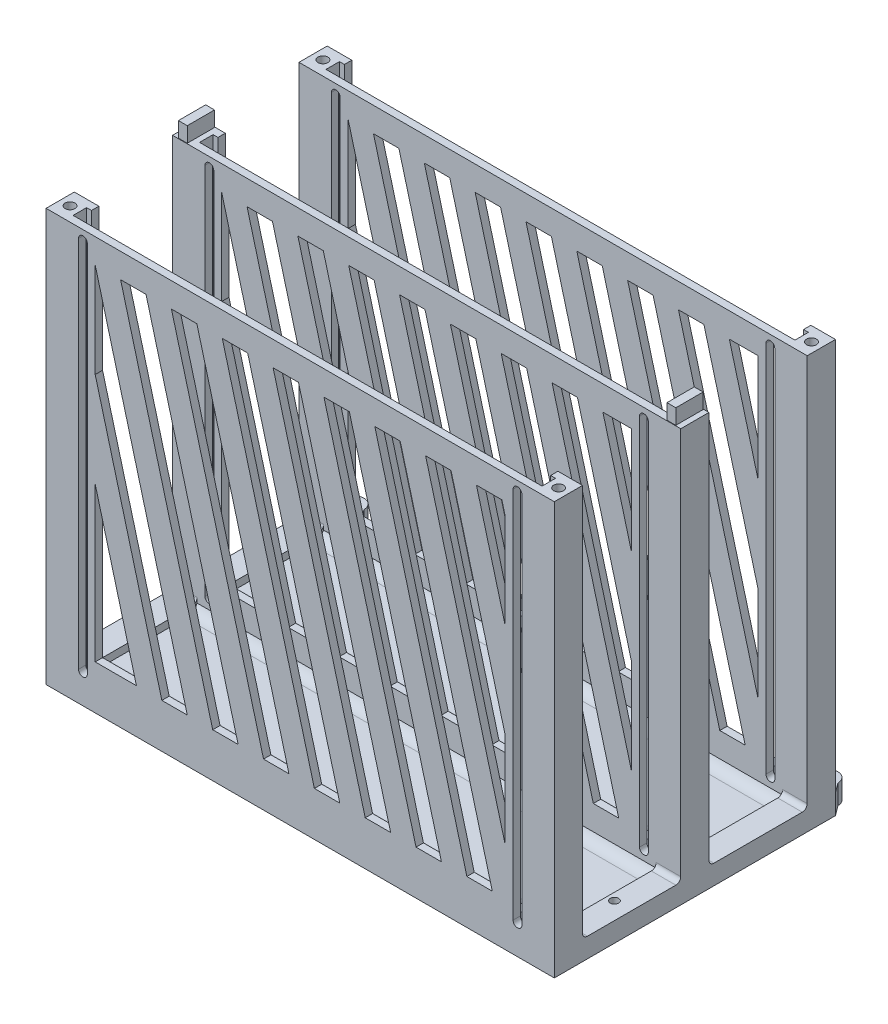
SolidWorks part; units mm, degrees
ref_plane "Front Plane" through (0, 0, 0) normal (0, 0, 1) x (1, 0, 0)
ref_plane "Top Plane" through (0, 0, 0) normal (0, 1, 0) x (1, 0, 0)
ref_plane "Right Plane" through (0, 0, 0) normal (1, 0, 0) x (0, 0, -1)
sketch "Sketch1" plane through (0, 0, 0) normal (0, 1, 0) x (1, 0, 0)
  line L0 (-95.5, 0) -> (95.5, 0) construction
  line L5 (-95.5, 2.75) -> (-93.5, 2.75)
  line L6 (-95.5, -2.75) -> (-95.5, 2.75)
  line L7 (-93.5, 2.75) -> (-93.5, 5.75)
  line L8 (-93.5, 5.75) -> (-103.5, 5.75)
  line L9 (-103.5, 5.75) -> (-103.5, -5.75)
  line L10 (-103.5, -5.75) -> (-93.5, -5.75)
  line L11 (-93.5, -5.75) -> (-93.5, -2.75)
  line L12 (-93.5, -2.75) -> (-95.5, -2.75)
  line L13 (-93.5, -2.75) -> (-93.5, -36.1204) construction
  line L14 (0, -55) -> (0, 55) construction
  line L15 (93.5, -5.75) -> (93.5, -2.75)
  line L16 (103.5, -5.75) -> (93.5, -5.75)
  line L17 (103.5, 5.75) -> (103.5, -5.75)
  line L18 (93.5, 5.75) -> (103.5, 5.75)
  line L19 (93.5, 2.75) -> (93.5, 5.75)
  line L20 (95.5, 2.75) -> (93.5, 2.75)
  line L21 (95.5, -2.75) -> (95.5, 2.75)
  line L22 (93.5, -2.75) -> (95.5, -2.75)
  line L23 (-93.5, 5.75) -> (93.5, 5.75)
  line L24 (-93.5, -5.75) -> (93.5, -5.75)
  line L25 (-93.5, -2.75) -> (93.5, -2.75)
  line L26 (93.5, 2.75) -> (-93.5, 2.75)
  line L27 (-93.5, -54.25) -> (-95.5, -54.25)
  line L28 (-95.5, -54.25) -> (-95.5, -48.75)
  line L29 (-95.5, -48.75) -> (-93.5, -48.75)
  line L30 (-93.5, -48.75) -> (-93.5, -45.75)
  line L31 (-93.5, -45.75) -> (-103.5, -45.75)
  line L32 (-103.5, -45.75) -> (-103.5, -57.25)
  line L33 (-103.5, -57.25) -> (-93.5, -57.25)
  line L34 (-93.5, -57.25) -> (-93.5, -54.25)
  line L35 (93.5, -57.25) -> (93.5, -54.25)
  line L36 (93.5, -54.25) -> (95.5, -54.25)
  line L37 (95.5, -54.25) -> (95.5, -48.75)
  line L38 (95.5, -48.75) -> (93.5, -48.75)
  line L39 (93.5, -48.75) -> (93.5, -45.75)
  line L40 (93.5, -45.75) -> (103.5, -45.75)
  line L41 (103.5, -45.75) -> (103.5, -57.25)
  line L42 (103.5, -57.25) -> (93.5, -57.25)
  line L43 (-93.5, -45.75) -> (93.5, -45.75)
  line L44 (93.5, -48.75) -> (-93.5, -48.75)
  line L45 (-93.5, -54.25) -> (93.5, -54.25)
  line L46 (-93.5, -57.25) -> (93.5, -57.25)
  line L47 (-93.5, -105.75) -> (-95.5, -105.75)
  line L48 (-95.5, -105.75) -> (-95.5, -100.25)
  line L49 (-95.5, -100.25) -> (-93.5, -100.25)
  line L50 (-93.5, -100.25) -> (-93.5, -97.25)
  line L51 (-93.5, -97.25) -> (-103.5, -97.25)
  line L52 (-103.5, -97.25) -> (-103.5, -108.75)
  line L53 (-103.5, -108.75) -> (-93.5, -108.75)
  line L54 (-93.5, -108.75) -> (-93.5, -105.75)
  line L55 (93.5, -108.75) -> (93.5, -105.75)
  line L56 (93.5, -105.75) -> (95.5, -105.75)
  line L57 (95.5, -105.75) -> (95.5, -100.25)
  line L58 (95.5, -100.25) -> (93.5, -100.25)
  line L59 (93.5, -100.25) -> (93.5, -97.25)
  line L60 (93.5, -97.25) -> (103.5, -97.25)
  line L61 (103.5, -97.25) -> (103.5, -108.75)
  line L62 (103.5, -108.75) -> (93.5, -108.75)
  line L63 (-93.5, -97.25) -> (93.5, -97.25)
  line L64 (93.5, -100.25) -> (-93.5, -100.25)
  line L65 (-93.5, -105.75) -> (93.5, -105.75)
  line L66 (-93.5, -108.75) -> (93.5, -108.75)
  line L67 (-103.5, -5.75) -> (-103.5, -45.75)
  line L68 (-93.5, -5.75) -> (-93.5, -45.75)
  line L69 (93.5, -5.75) -> (93.5, -45.75)
  line L70 (103.5, -5.75) -> (103.5, -45.75)
  line L71 (103.5, -57.25) -> (103.5, -97.25)
  line L72 (93.5, -97.25) -> (93.5, -57.25)
  line L73 (-103.5, -97.25) -> (-103.5, -57.25)
  line L74 (-93.5, -97.25) -> (-93.5, -57.25)
  line L75 (0, 5.75) -> (0, 9.75) construction
  line L76 (-96.5, 9.75) -> (96.5, 9.75) construction
  line L77 (-100.5, 9.75) -> (-103.5, 5.75)
  line L78 (-96.5, 8.05) -> (-96.5, 5.75) construction
  line L79 (-92.5, 9.75) -> (-89.5, 5.75)
  line L80 (92.5, 9.75) -> (89.5, 5.75)
  line L81 (100.5, 9.75) -> (103.5, 5.75)
  line L82 (-103.5, -51.5) -> (103.5, -51.5) construction
  line L83 (100.5, -112.75) -> (103.5, -108.75)
  line L84 (92.5, -112.75) -> (89.5, -108.75)
  line L85 (-92.5, -112.75) -> (-89.5, -108.75)
  line L86 (-100.5, -112.75) -> (-103.5, -108.75)
  circle A1 centre (96.5, 9.75) radius 1.7
  circle A2 centre (-96.5, 9.75) radius 1.7
  circle A4 centre (-96.5, 9.75) radius 4
  circle A5 centre (96.5, 9.75) radius 4
  circle A7 centre (96.5, 9.75) radius 1.7
  circle A8 centre (96.5, -112.75) radius 1.7
  circle A9 centre (96.5, -112.75) radius 4
  circle A10 centre (-96.5, -112.75) radius 1.7
  circle A12 centre (-96.5, -112.75) radius 4
  point P3 (0, 0)
  point P6 (95.5, 0)
  point P9 (-95.5, 0)
  point P61 (0, 9.75)
  dimension "D11" = 3.4
  dimension "D12" = 4
  dimension "D1" = 191
  dimension "D2" = 5.5
  dimension "D3" = 2
  dimension "D4" = 3
  dimension "D5" = 3
  dimension "D6" = 2
  dimension "D7" = 10
  dimension "D8" = 193
  dimension "D10" = 40
  dimension "D9" = 3
extrude "Boss-Extrude1" add sketch "Sketch1" against normal blind 3.2 contours L53 L54 L47 L48 L49 L50 L51 L52 | L54 L66 L55 L65 | L64 L59 L63 L50 | L34 L46 L35 L45 | L33 L34 L27 L28 L29 L30 L31 L32 | L44 L39 L43 L30 | L25 L11 L24 L15 | L26 L19 L23 L7 | L22 L15 L16 L17 L18 L19 L20 L21 | L42 L41 L40 L39 L38 L37 L36 L35 | L62 L61 L60 L59 L58 L57 L56 L55 | L11 L12 L6 L5 L7 L8 L9 L10 | L51 L74 L33 L73 | L68 L10 L67 L31 | L72 L60 L71 L42 | L70 L16 L69 L40 region at (-98.9231, 0, 0) region at (0, 0, -4.25) region at (98.9231, 0, 0) region at (0, 0, 4.25) region at (-98.5, 0, 25.75) region at (98.5, 0, 25.75) region at (0, 0, 47.25) region at (-98.9231, 0, 51.5) region at (98.9231, 0, 51.5) region at (-98.5, 0, 77.25) region at (0, 0, 55.75) region at (-98.9231, 0, 103) region at (98.5, 0, 77.25) region at (0, 0, 98.75) region at (98.9231, 0, 103) region at (0, 0, 107.25)
extrude "Boss-Extrude2" add sketch "Sketch1<4>" along normal blind 160 contours L53 L54 L47 L48 L49 L50 L51 L52 | L33 L34 L27 L28 L29 L30 L31 L32 | L11 L12 L6 L5 L7 L8 L9 L10 | L62 L61 L60 L59 L58 L57 L56 L55 | L42 L41 L40 L39 L38 L37 L36 L35 | L22 L15 L16 L17 L18 L19 L20 L21 region at (-98.9231, 0, 0) region at (98.9231, 0, 0) region at (-98.9231, 0, 51.5) region at (98.9231, 0, 51.5) region at (-98.9231, 0, 103) region at (98.9231, 0, 103)
sketch "Sketch1<4>" plane through (0, 0, 0) normal (0, 1, 0) x (1, 0, 0) same geometry as "Sketch1"
extrude "Boss-Extrude3" add sketch "Sketch1<5>" against normal blind 5 from offset 3 contours L53 L54 L47 L48 L49 L50 L51 L52 | L54 L66 L55 L65 | L47 L65 L56 L57 L58 L64 L49 L48 | L64 L59 L63 L50 | L51 L74 L33 L73 | L33 L34 L27 L28 L29 L30 L31 L32 | L34 L46 L35 L45 | L44 L39 L43 L30 | L68 L10 L67 L31 | L11 L12 L6 L5 L7 L8 L9 L10 | L25 L11 L24 L15 | L26 L19 L23 L7 | L22 L15 L16 L17 L18 L19 L20 L21 | L70 L16 L69 L40 | L42 L41 L40 L39 L38 L37 L36 L35 | L72 L60 L71 L42 | L62 L61 L60 L59 L58 L57 L56 L55 | L27 L45 L36 L37 L38 L44 L29 L28 | L20 L26 L5 L6 L12 L25 L22 L21 | L74 L63 L72 L46 | L69 L24 L68 L43 region at (-98.9231, 0, 0) region at (0, 0, 0) region at (0, 0, -4.25) region at (98.9231, 0, 0) region at (0, 0, 4.25) region at (-98.5, 0, 25.75) region at (0, 0, 25.75) region at (98.5, 0, 25.75) region at (0, 0, 47.25) region at (-98.9231, 0, 51.5) region at (98.9231, 0, 51.5) region at (0, 0, 51.5) region at (-98.5, 0, 77.25) region at (0, 0, 55.75) region at (0, 0, 77.25) region at (-98.9231, 0, 103) region at (98.5, 0, 77.25) region at (0, 0, 98.75) region at (98.9231, 0, 103) region at (0, 0, 103) region at (0, 0, 107.25) offset against normal yes
sketch "Sketch1<5>" plane through (0, 0, 0) normal (0, 1, 0) x (1, 0, 0) same geometry as "Sketch1"
fillet "Fillet1" radius 5 4 edges at (0, -3, 45.75) (0, -3, 5.75) (0, -3, 57.25) (0, -3, 97.25)
sketch "Sketch2" plane through (0, 160, 0) normal (0, 1, 0) x (1, 0, 0)
  line L0 (-95.5, 2.75) -> (-103.5, 2.75) construction
  line L1 (-103.5, 5.75) -> (-103.5, -5.75) construction
  line L2 (-95.5, -2.75) -> (-103.5, -2.75) construction
  line L3 (-99.5, 2.75) -> (-99.5, -2.75) construction
  line L4 (0, -62.975) -> (0, 62.975) construction
  line L5 (-95.5, -48.75) -> (-103.5, -48.75) construction
  line L6 (-103.5, -45.75) -> (-103.5, -57.25) construction
  line L7 (-95.5, -54.25) -> (-103.5, -54.25) construction
  line L8 (-99.5, -48.75) -> (-99.5, -54.25) construction
  line L9 (-103.5, -51.5) -> (103.5, -51.5) construction
  line L10 (103.5, -45.75) -> (103.5, -57.25) construction
  line L12 (0, -45.75) -> (0, -57.25) construction
  line L13 (-93.5, -45.75) -> (93.5, -45.75) construction
  line L14 (-93.5, -57.25) -> (93.5, -57.25) construction
  line L15 (97.7, -45.95) -> (101.3, -45.95)
  line L16 (101.3, -57.05) -> (101.3, -45.95)
  line L17 (-103.5, -45.75) -> (-93.5, -45.75)
  line L21 (-103.5, -57.25) -> (-103.5, -45.75)
  line L26 (-97.7, -57.05) -> (-101.3, -57.05)
  line L27 (-97.7, -57.05) -> (-97.7, -45.95)
  line L28 (-97.7, -45.95) -> (-101.3, -45.95)
  line L29 (-101.3, -57.05) -> (-101.3, -45.95)
  line L30 (-99.5, -45.95) -> (-99.5, -57.05) construction
  line L31 (-97.7, -51.5) -> (-101.3, -51.5) construction
  line L37 (99.5, -45.75) -> (99.5, -57.25) construction
  line L38 (101.3, -51.5) -> (97.7, -51.5) construction
  line L39 (97.7, -57.05) -> (101.3, -57.05)
  line L40 (97.7, -57.05) -> (97.7, -45.95)
  circle A0 centre (-99.5, 0) radius 2
  circle A1 centre (99.5, 0) radius 2
  circle A2 centre (-99.5, -51.5) radius 2 construction
  circle A3 centre (99.5, -51.5) radius 2 construction
  circle A4 centre (-99.5, -103) radius 2
  circle A5 centre (99.5, -103) radius 2
  dimension "D1" = 4
  dimension "D3" = 2.2
  dimension "D4" = 0.2
  dimension "D2" = 3
extrude "Cut-Extrude1" cut sketch "Sketch2" against normal blind 5 contours A0 | A1 | A5 | A4 region at (-99.5, 160, 0) region at (99.5, 160, 0) region at (-99.5, 160, 103) region at (99.5, 160, 103)
fillet "Fillet2" radius 2 8 edges at (-98.5, 0, 5.75) (-98.5, 0, 57.25) (-98.5, 0, 45.75) (-98.5, 0, 97.25) (98.5, 0, 45.75) (98.5, 0, 5.75) (98.5, 0, 57.25) (98.5, 0, 97.25)
sketch "Sketch3" plane through (0, 0, 108.75) normal (0, 0, 1) x (1, 0, 0)
  line L0 (-93.5, 160) -> (93.5, 160)
  line L1 (-93.5, 160) -> (93.5, 0) construction
  line L2 (-93.5, 160) -> (93.5, 160)
  line L3 (-93.5, 160) -> (-93.5, 0)
  line L4 (-93.5, 0) -> (93.5, 0)
  line L5 (93.5, 160) -> (93.5, 0)
  line L6 (-83.5, 150) -> (-45.9871, 10)
  line L7 (-83.5, 10) -> (83.5, 10)
  line L8 (-83.5, 10) -> (-83.5, 150)
  line L9 (-83.5, 150) -> (83.5, 150)
  line L10 (83.5, 10) -> (83.5, 150)
  line L11 (0, 150) -> (0, 10) construction
  line L12 (-83.5, 80) -> (83.5, 80) construction
  line L13 (-73.1472, 150) -> (-35.6344, 10)
  line L14 (-52.4417, 150) -> (-14.9288, 10)
  line L15 (-62.7945, 150) -> (-25.2816, 10)
  line L16 (-31.7362, 150) -> (5.7767, 10)
  line L17 (-42.089, 150) -> (-4.5761, 10)
  line L18 (-11.0307, 150) -> (26.4822, 10)
  line L19 (-21.3834, 150) -> (16.1295, 10)
  line L20 (9.6749, 150) -> (47.1877, 10)
  line L21 (-0.6779, 150) -> (36.835, 10)
  line L22 (30.3804, 150) -> (67.8933, 10)
  line L23 (20.0276, 150) -> (57.5405, 10)
  line L24 (51.0859, 150) -> (88.5988, 10)
  line L25 (40.7331, 150) -> (78.246, 10)
  line L26 (71.7914, 150) -> (83.5, 106.303)
  line L27 (61.4387, 150) -> (83.5, 67.666)
  line L28 (-88.5, 160) -> (-88.5, 156) construction
  line L29 (82.1442, 150) -> (83.5, 144.94)
  line L30 (-56.3399, 10) -> (-83.5, 111.363)
  line L31 (-83.5, 72.7259) -> (-66.6926, 10)
  line L32 (98.412, 127.9247) -> (99.5066, 123.8397) [skipped]
  line L33 (-90.3, 156) -> (-90.3, 4)
  line L34 (-86.7, 4) -> (-86.7, 156)
  line L35 (86.7, 4) -> (86.7, 156)
  line L36 (90.3, 156) -> (90.3, 4)
  circle A1 centre (-88.5, 156) radius 1.8
  circle A2 centre (-88.5, 4) radius 1.8
  circle A3 centre (88.5, 4) radius 1.8
  circle A4 centre (88.5, 156) radius 1.8
  point P6 (0, 80)
  point P40 (-88.5, 160)
  point P53 (-88.5, 0)
  line M38 (93.5, 160) -> (93.5, 0)
  line M39 (93.5, 0) -> (-93.5, 0)
  line M40 (-93.5, 0) -> (-93.5, 160)
  dimension "D11" = 3.6
  dimension "D1" = 10
  dimension "D2" = 10
  dimension "D3" = 15
  dimension "D4" = 10
  dimension "D6" = 10
  dimension "D7" = 10
  dimension "D8" = 10
  dimension "D9" = 5
  dimension "D10" = 4
  dimension "D5" = 9
extrude "Boss-Extrude4" add sketch "Sketch3" against normal up to vertex (3 mm away) contours L0 L10 L7 L8 L9 M40 M39 M38 | L8 L31 L7 L30 | L13 L9 L6 L7 | L9 L15 L7 L14 | L9 L17 L7 L16 | L9 L19 L7 L18 | L9 L21 L7 L20 | L9 L23 L7 L22 | L9 L25 L7 L24 | L9 L27 L10 L26 | L9 L29 L10 region at (0, 157.5389, 108.75) region at (-59.5672, 80, 108.75) region at (-72.305, 51.7804, 108.75) region at (-38.8617, 80, 108.75) region at (-18.1561, 80, 108.75) region at (2.5494, 80, 108.75) region at (23.2549, 80, 108.75) region at (43.9604, 80, 108.75) region at (63.9549, 82.2044, 108.75) region at (74.793, 117.5052, 108.75) region at (83.0481, 148.3133, 108.75) up to point (-95.5, -3, 105.75)
sketch "Sketch4" plane through (0, 0, 57.25) normal (0, 0, 1) x (1, 0, 0)
  line L0 (-93.5, 160) -> (93.5, 0) construction
  line L1 (-93.5, 160) -> (93.5, 160)
  line L2 (-93.5, 160) -> (-93.5, 0)
  line L3 (-93.5, 0) -> (93.5, 0)
  line L4 (93.5, 160) -> (93.5, 0)
  line L5 (-83.5, 150) -> (-45.9871, 10)
  line L6 (-83.5, 10) -> (83.5, 10)
  line L7 (-83.5, 10) -> (-83.5, 150)
  line L8 (-83.5, 150) -> (83.5, 150)
  line L9 (83.5, 10) -> (83.5, 150)
  line L10 (0, 150) -> (0, 10) construction
  line L11 (-83.5, 80) -> (83.5, 80) construction
  line L12 (-73.1472, 150) -> (-35.6344, 10)
  line L13 (-52.4417, 150) -> (-14.9288, 10)
  line L14 (-62.7945, 150) -> (-25.2816, 10)
  line L15 (-31.7362, 150) -> (5.7767, 10)
  line L16 (-42.089, 150) -> (-4.5761, 10)
  line L17 (-11.0307, 150) -> (26.4822, 10)
  line L18 (-21.3834, 150) -> (16.1295, 10)
  line L19 (9.6749, 150) -> (47.1877, 10)
  line L20 (-0.6779, 150) -> (36.835, 10)
  line L21 (30.3804, 150) -> (67.8933, 10)
  line L22 (20.0276, 150) -> (57.5405, 10)
  line L23 (51.0859, 150) -> (88.5988, 10)
  line L24 (40.7331, 150) -> (78.246, 10)
  line L25 (71.7914, 150) -> (83.5, 106.303)
  line L26 (61.4387, 150) -> (83.5, 67.666)
  line L27 (-56.3399, 10) -> (-83.5, 111.363)
  line L28 (-66.6926, 10) -> (-83.5, 72.7259)
  line L29 (99.997, 122.0096) -> (101, 118.2662) [skipped]
  line L30 (89.6442, 122.0096) -> (91, 116.9497) [skipped]
  point P5 (0, 80)
  line M15 (93.5, 160) -> (93.5, 2)
  dimension "D1" = 10
  dimension "D2" = 10
  dimension "D3" = 15
  dimension "D4" = 10
  dimension "D6" = 10
  dimension "D7" = 10
  dimension "D8" = 10
  dimension "D5" = 9
extrude "Boss-Extrude5" add sketch "Sketch4" against normal blind 3 contours L4 L1 L2 L3 L9 L6 L7 L8 M15 | L12 L8 L5 L6 | L28 L6 L27 L7 | L8 L14 L6 L13 | L8 L16 L6 L15 | L8 L18 L6 L17 | L8 L20 L6 L19 | L8 L22 L6 L21 | L8 L24 L6 L23 | L8 L26 L9 L25 region at (0, 157.5389, 57.25) region at (-59.5672, 80, 57.25) region at (-72.305, 51.7804, 57.25) region at (-38.8617, 80, 57.25) region at (-18.1561, 80, 57.25) region at (2.5494, 80, 57.25) region at (23.2549, 80, 57.25) region at (43.9604, 80, 57.25) region at (63.9549, 82.2044, 57.25) region at (74.793, 117.5052, 57.25)
pattern_linear "LPattern1" count 2 spacing 51.5 along (0, 0, -1) of "Boss-Extrude5"
sketch "Sketch5" plane through (0, 0, 0) normal (0, 1, 0) x (1, 0, 0)
  line L0 (-103.5, -51.5) -> (103.5, -51.5) construction
  line L1 (-103.5, -45.75) -> (-103.5, -57.25) construction
  line L2 (103.5, -45.75) -> (103.5, -57.25) construction
  line L3 (0, 5.75) -> (0, -108.75) construction
  line L4 (-93.5, 5.75) -> (93.5, 5.75) construction
  line L5 (103.5, -108.75) -> (-103.5, -108.75) construction
  line L9 (-96.5, -25.75) -> (96.5, -25.75) construction
  line L10 (-103.5, -25.75) -> (-93.5, -25.75) construction
  line L11 (-103.5, -7.75) -> (-103.5, -43.75) construction
  line L12 (-93.5, -41.1674) -> (-93.5, -10.3326) construction
  circle A0 centre (96.5, -25.75) radius 1.7
  circle A1 centre (-96.5, -25.75) radius 1.7
  circle A2 centre (-96.5, -77.25) radius 1.7
  circle A3 centre (96.5, -77.25) radius 1.7
  point P21 (0, -25.75)
  point P27 (-96.5, -25.75)
  dimension "D2" = 3.4
  dimension "D1" = 193
extrude "BASEPLATE HOLES" cut sketch "Sketch5" against normal blind 10 contours A2 | A3 region at (-96.5, 0, 77.25) region at (96.5, 0, 77.25)
extrude "Boss-Extrude6" add sketch "Sketch2<4>" along normal blind 6.2 contours L21 | L29 L26 L27 L17 | L40 L39 L16 L15 region at (99.5, 160, 51.5) region at (-99.5, 160, 51.5)
sketch "Sketch2<4>" plane through (0, 160, 0) normal (0, 1, 0) x (1, 0, 0) same geometry as "Sketch2"
extrude "Cut-Extrude3" cut sketch "Sketch3<3>" against normal through all contours L33 A2 L34 A1 | A2 | A1 | A4 | L36 A4 L35 A3 | A3 region at (88.5, 80, 108.75) region at (88.5, 4, 108.75) region at (88.5, 156, 108.75) region at (-88.5, 80, 108.75) region at (-88.5, 156, 108.75) region at (-88.5, 4, 108.75)
sketch "Sketch3<3>" plane through (0, 0, 108.75) normal (0, 0, 1) x (1, 0, 0) same geometry as "Sketch3"
extrude "BASEPLATEHOLES2" add sketch "Sketch1<6>" against normal up to surface (8 mm away) contours A4 L77 L8 | A4 A2 | A4 L8 L23 L79 | L81 A5 L18 | A5 A1 | L18 A5 L80 L23 region at (-92.1892, 0, -6.9232) region at (-100.8108, 0, -6.9232) region at (-99.2484, 0, -7.0016) region at (92.1892, 0, -6.9232) region at (100.8108, 0, -6.9232) region at (93.7516, 0, -7.0016) up to face at (0, -8, 51.5)
sketch "Sketch1<6>" plane through (0, 0, 0) normal (0, 1, 0) x (1, 0, 0) same geometry as "Sketch1"
